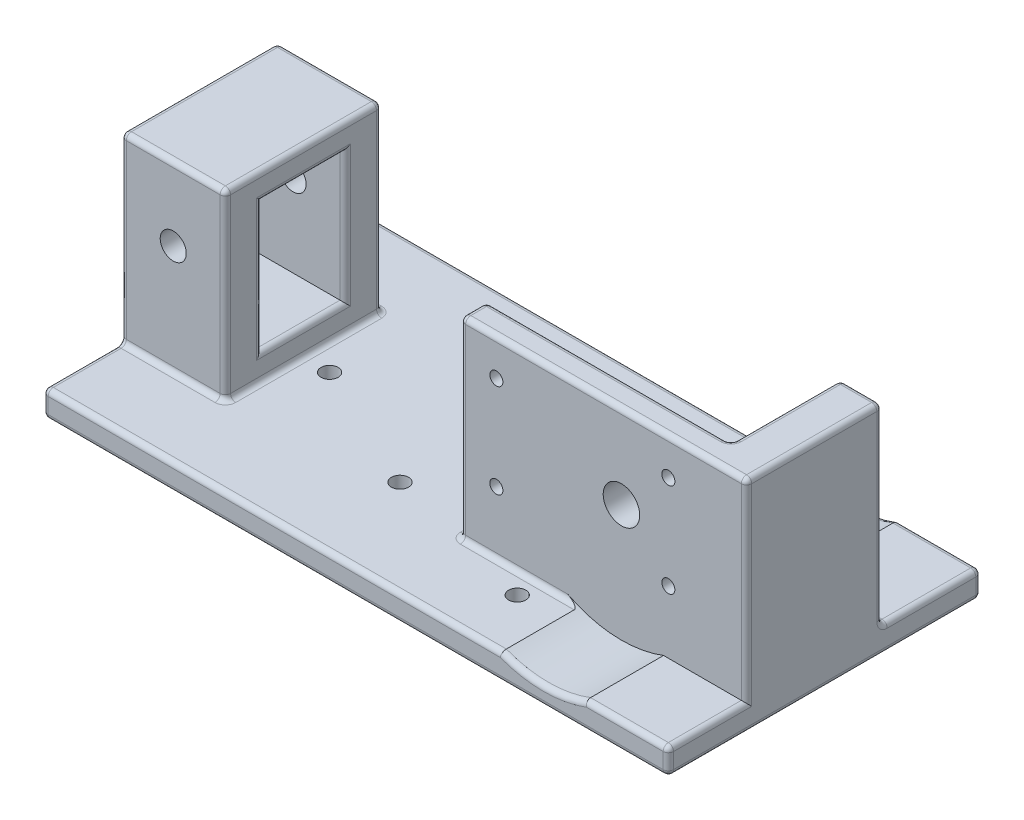
SolidWorks part; units mm, degrees
ref_plane "前视基准面" through (0, 0, 0) normal (0, 0, 1) x (1, 0, 0)
ref_plane "上视基准面" through (0, 0, 0) normal (0, 1, 0) x (1, 0, 0)
ref_plane "右视基准面" through (0, 0, 0) normal (1, 0, 0) x (0, 0, -1)
other "Configuration Table"
sketch "草图1" plane through (0, 0, 0) normal (0, 0, 1) x (1, 0, 0)
  line L0 (17, 9) -> (17, -9) construction
  line L1 (17, -9) -> (-16, -9) construction
  line L2 (-16, -9) -> (-16, 9) construction
  line L3 (-16, 9) -> (17, 9) construction
  line L7 (-22.9, 16) -> (24, 16)
  line L8 (-22.9, 16) -> (-22.9, -16)
  line L9 (-22.9, -16) -> (24, -16)
  line L10 (24, 16) -> (24, -16)
  circle A20 centre (17, 9) radius 1.25
  circle A21 centre (17, -9) radius 1.25
  circle A23 centre (-16, -9) radius 1.25
  circle A24 centre (-16, 9) radius 1.25
  circle A26 centre (8, 0) radius 3.5
  dimension "D1" = 2.5
  dimension "D4" = 8
  dimension "D3" = 16
  dimension "D8" = 7
  dimension "D2" = 17
  dimension "D5" = 33
  dimension "D6" = 18
  dimension "D7" = 9
  dimension "D9" = 24
  dimension "D10" = 22.9
  dimension "D11" = 16
extrude "凸台-拉伸1" add sketch "草图1" along normal blind 5
sketch "草图2" plane through (0, -16, 0) normal (0, -1, 0) x (1, 0, 0)
  line L0 (-22.9, 5) -> (24, 5) construction
  line L1 (-88, 5) -> (32, 5)
  line L2 (-88, 5) -> (-88, -25)
  line L3 (-88, -25) -> (32, -25)
  line L4 (32, 5) -> (32, -25)
  line L5 (24, 5) -> (24, 0) construction
  dimension "D1" = 30
  dimension "D2" = 120
  dimension "D3" = 8
extrude "凸台-拉伸2" add sketch "草图2" along normal blind 5
sketch "草图3" plane through (0, -16, 0) normal (0, 1, 0) x (1, 0, 0)
  line L1 (-88, -5) -> (-68, -5)
  line L2 (-88, -5) -> (-88, 2)
  line L3 (-88, 2) -> (-68, 2)
  line L4 (-68, -5) -> (-68, 2)
  line L5 (-88, 25) -> (-68, 25)
  line L6 (-88, 25) -> (-88, 18)
  line L7 (-88, 18) -> (-68, 18)
  line L8 (-68, 25) -> (-68, 18)
  dimension "D1" = 7
  dimension "D2" = 7
  dimension "D3" = 20
  dimension "D4" = 20
extrude "凸台-拉伸3" add sketch "草图3" along normal blind 30 separate body
sketch "草图4" plane through (0, 0, 5) normal (0, 0, 1) x (1, 0, 0)
  line L0 (8, 0) -> (-78, 0) construction
  line L1 (-68, 14) -> (-68, -16) construction
  circle A0 centre (-78, 0) radius 2.5
  dimension "D2" = 5
  dimension "D1" = 10
extrude "切除-拉伸1" cut sketch "草图4" against normal through all
sketch "草图5" plane through (0, 14, 0) normal (0, 1, 0) x (1, 0, 0)
  line L1 (-68, -5) -> (-88, -5)
  line L2 (-68, -5) -> (-68, 25)
  line L3 (-68, 25) -> (-88, 25)
  line L4 (-88, -5) -> (-88, 25)
extrude "凸台-拉伸4" add sketch "草图5" against normal blind 5
sketch "草图6" plane through (0, -21, 0) normal (0, -1, 0) x (1, 0, 0)
  line L0 (-88, -25) -> (32, -25) construction
  line L1 (-88, 20) -> (32, 20)
  line L2 (-88, 20) -> (-88, -40)
  line L3 (-88, -40) -> (32, -40)
  line L4 (32, 20) -> (32, -40)
  line L5 (-88, 5) -> (-88, -25) construction
  dimension "D1" = 120
  dimension "D2" = 60
  dimension "D3" = 15
extrude "凸台-拉伸5" add sketch "草图6" along normal blind 5
sketch "草图7" plane through (0, 0, -40) normal (0, 0, -1) x (-1, 0, 0)
  circle A0 centre (-8, 0) radius 22.5
  point P3 (0, 0)
  dimension "D1" = 45
extrude "切除-拉伸2" cut sketch "草图7" along normal up to surface (15 mm away) from surface at -60 up to face at (-24.58, -4.6, 5) starting at face at (-28, -23.5, 20)
sketch "草图8" plane through (0, 0, -40) normal (0, 0, -1) x (-1, 0, 0)
  circle A0 centre (-8, 0) radius 22.5 construction
  circle A1 centre (-8, 0) radius 22.5
extrude "切除-拉伸3" cut sketch "草图8" against normal blind 18
sketch "草图9" plane through (0, -26, 0) normal (0, -1, 0) x (1, 0, 0)
  line L4 (-38, 1.5) -> (-38, -21.5) construction
  line L5 (-88, -10) -> (32, -10) construction
  line L6 (-88, 20) -> (-88, -40) construction
  line L7 (32, -40) -> (32, 20) construction
  circle A4 centre (-63, -10) radius 1.65
  circle A5 centre (-38, 1.5) radius 1.65
  circle A6 centre (-38, -21.5) radius 1.65
  point P20 (-38, -10)
  dimension "D6" = 3.3
  dimension "D7" = 23
  dimension "D8" = 25
  dimension "D9" = 25
extrude "切除-拉伸4" cut sketch "草图9" against normal up to surface (5 mm away) up to face at (-44.0389, -21, -32.5)
sketch "草图12" plane through (0, 0, -25) normal (0, 0, -1) x (-1, 0, 0)
  line L0 (88, -21) -> (0.0777, -21) construction
  line L1 (68, -16) -> (22.9, -16)
  line L2 (68, -16) -> (68, -21)
  line L3 (68, -21) -> (22.9, -21)
  line L4 (22.9, -16) -> (22.9, -21)
  line L5 (22.9, 16) -> (22.9, -16) construction
extrude "切除-拉伸5" cut sketch "草图12" against normal up to surface (30 mm away) up to face at (-19.15, -7.4583, 5)
sketch "草图14" plane through (0, 0, -25) normal (0, 0, -1) x (-1, 0, 0)
  line L1 (-32, -16) -> (22.9, -16)
  line L2 (-32, -16) -> (-32, -21)
  line L3 (-32, -21) -> (22.9, -21)
  line L4 (22.9, -16) -> (22.9, -21)
extrude "切除-拉伸7" cut sketch "草图14" against normal up to surface (25 mm away) up to face at (0.55, 0, 0)
sketch "草图15" plane through (0, 0, 0) normal (0, 0, -1) x (-1, 0, 0)
  line L1 (-24, -16) -> (-32, -16)
  line L2 (-24, -16) -> (-24, -21)
  line L3 (-24, -21) -> (-32, -21)
  line L4 (-32, -16) -> (-32, -21)
extrude "切除-拉伸8" cut sketch "草图15" against normal up to surface (5 mm away) up to face at (-78, -3.5, 5)
fillet "圆角2" radius 1 41 edges at (-88, -21, 12.5) (-88, -21, -32.5) (-88, -23.5, 20) (-44.0389, -21, -40) (-88, -23.5, -40) (32, -23.5, -40) (24.0389, -21, 20) (32, -23.5, 20) (-88, -26, -10) (-28, -26, -40) (-28, -26, 20) (-44.0389, -21, 20) (-11.4889, -21, 5) (8, -22.5, 20) (24.0389, -21, -40) (8, -22.5, -40) (-78, -21, 5) (-68, -21, -10) (-22.9, -21, 2.5) (-68, -16, -10) (8, -22.5, -22) (0.55, -21, 0) (-88, -3.5, 5) (-88, -3.5, -25) (-78, -21, -25) (-22.9, -2.5, 5) (-88, -16, -10) (-68, -3.5, 5) (-88, 14, -10) (-78, 14, 5) (-68, 14, -10) (-22.9, -2.5, 0) (-68, -3.5, -25) (-78, 14, -25) (-68, -3.5, -18) (-88, -3.5, -18) (-88, -3.5, -2) (-68, -3.5, -2) (-22.9, 16, 2.5) (-68, 9, -10) (-88, 9, -10)
sketch "草图16" plane through (24, 0, 0) normal (1, 0, 0) x (0, 0, -1)
  line L0 (39, -26) -> (39, -21) construction
  line L1 (-5, -21) -> (21, -21)
  line L2 (-5, -21) -> (-5, 16)
  line L3 (-5, 16) -> (21, 16)
  line L4 (21, -21) -> (21, 16)
  dimension "D1" = 18
extrude "凸台-拉伸6" add sketch "草图16" along normal up to surface (8 mm away) up to face at (32, -23.5, -10)
fillet "圆角3" radius 1 21 edges at (5.05, 16, 5) (32, -21, -30) (24, -2, 0) (32, -26, -10) (24, -20.7071, -0.2929) (-22.6071, 15.7071, 0.2929) (-22.6071, 15.7071, 4.7071) (31.7071, -21.2929, 19.7071) (31.7071, -25.7071, 19.7071) (31.7071, -25.7071, -39.7071) (31.7071, -21.2929, -39.7071) (32, -21, 12) (32, 16, -8) (28, 16, -21) (24, 16, -10.5) (32, -2.5, -21) (28, -21, -21) (24, -2.5, -21) (24, -21, -11) (32, -2.5, 5) (1.05, 16, 0)
sketch "草图18" plane through (0, -26, 0) normal (0, -1, 0) x (1, 0, 0)
  line L0 (-8, -39) -> (-8, 19) construction
  line L1 (-87, -39) -> (31, -39) construction
  line L2 (31, 19) -> (-87, 19) construction
  line L3 (32, 19) -> (32, -39) construction
  circle A0 centre (-8, -29) radius 1.65
  circle A1 centre (-8, -10) radius 1.65
  circle A2 centre (-8, 9) radius 1.65
  dimension "D4" = 3.3
  dimension "D1" = 40
  dimension "D2" = 10
  dimension "D3" = 10
extrude "切除-拉伸9" cut sketch "草图18" against normal up to surface (5 mm away) up to face at (-21.2356, -21, -12.7054)
